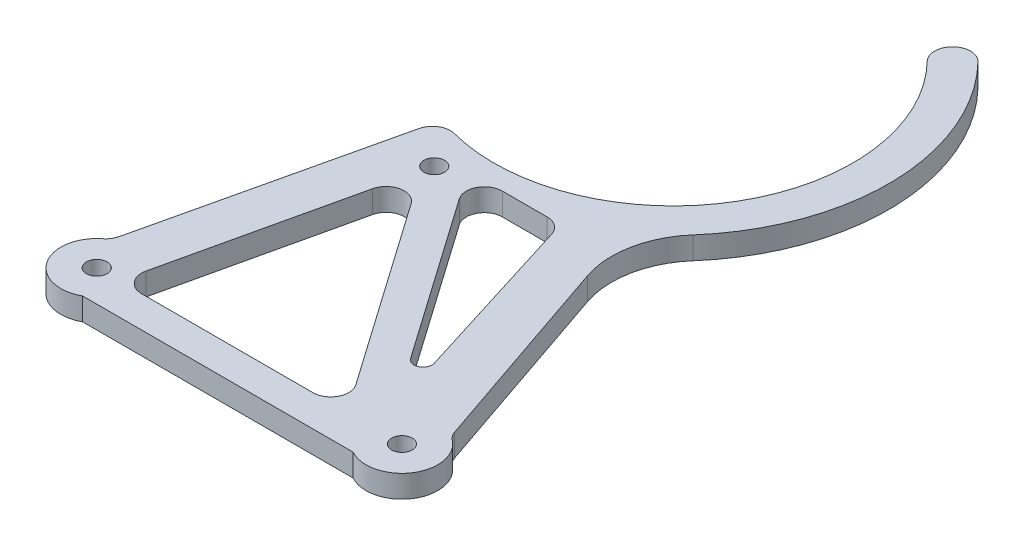
SolidWorks part; units mm, degrees
ref_plane "Front Plane" through (0, 0, 0) normal (0, 0, 1) x (1, 0, 0)
ref_plane "Top Plane" through (0, 0, 0) normal (0, 1, 0) x (1, 0, 0)
ref_plane "Right Plane" through (0, 0, 0) normal (1, 0, 0) x (0, 0, -1)
sketch "Sketch1" plane through (0, 0, 0) normal (0, 1, 0) x (1, 0, 0)
  line L0 (2.4593, 4.445) -> (40.7207, 4.445)
  line L1 (2.4593, -4.445) -> (40.7207, -4.445)
  circle A0 centre (0, 0) radius 1.4605
  circle A1 centre (0, 0) radius 5.08
  circle A2 centre (43.18, 0) radius 1.4605
  circle A3 centre (43.18, 0) radius 5.08
  dimension "D1" = 2.921
  dimension "D2" = 10.16
  dimension "D5" = 2.921
  dimension "D6" = 10.16
  dimension "D3" = 8.89
  dimension "D4" = 4.445
  dimension "D7" = 0
  dimension "D8" = 5.08
  dimension "D9" = 4.445
  dimension "D10" = 43.18
extrude "Boss-Extrude1" add sketch "Sketch1" along normal blind 3.175 contours A1 A0 | A3 L0 A1 L1 | A3 A2
sketch "Sketch3" plane through (0, 3.175, 0) normal (0, 1, 0) x (1, 0, 0)
  line L0 (31.75, 85.6456) -> (35.05, 89.5078)
  line L1 (-2.4593, 4.445) -> (35.6407, 4.445)
  line L3 (2.4593, 4.445) -> (40.7207, 4.445) construction
  line L4 (-2.4593, 4.445) -> (6.35, 42.545)
  line L5 (45.72, 4.3994) -> (33.02, 41.5706)
  arc A0 (6.35, 42.545) -> (31.75, 85.6456) centre (15.2501, 66.3347) ccw
  arc A1 (2.4593, 4.445) -> (2.4593, -4.445) centre (0, 0) ccw construction
  arc A3 (40.7207, -4.445) -> (40.7207, 4.445) centre (43.18, 0) ccw construction
  arc A4 (35.05, 89.5078) -> (33.02, 41.5706) centre (15.2501, 66.3347) cw
  circle A5 centre (43.18, 0) radius 1.4605 construction
  dimension "D1" = 25.4
  dimension "D10" = 0
  dimension "D7" = 0
  dimension "D8" = 30.48
  dimension "D2" = 160
  dimension "D3" = 25.4
  dimension "D4" = 38.1
  dimension "D5" = 0
  dimension "D6" = 6.35
  dimension "D9" = 30.48
  dimension "D11" = 5.08
  dimension "D12" = 12.7
  dimension "D13" = 2.54
extrude "Boss-Extrude3" add sketch "Sketch3" against normal blind 3.175
sketch "Sketch4" plane through (0, 3.175, 0) normal (0, 1, 0) x (1, 0, 0)
  line L2 (39.37, 0) -> (3.175, 0)
  line L3 (3.175, 0) -> (11.8398, 38.1)
  line L4 (11.8398, 38.1) -> (27.4954, 38.1)
  line L5 (27.4954, 38.1) -> (39.37, 0)
  line L6 (-2.4593, 4.445) -> (6.35, 42.545) construction
  line L7 (45.72, 4.3994) -> (33.02, 41.5706) construction
  line L8 (11.0899, 34.8025) -> (35.4588, 0)
  line L9 (14.4014, 38.1) -> (37.9988, 4.3994)
  circle A0 centre (43.18, 0) radius 1.4605 construction
  dimension "D1" = 3.175
  dimension "D2" = 3.81
  dimension "D3" = 6.35
  dimension "D4" = 6.35
  dimension "D5" = 0
  dimension "D6" = 38.1
  dimension "D7" = 55
  dimension "D8" = 55
  dimension "D9" = 5.08
  dimension "D10" = 2.54
extrude "Cut-Extrude1" cut sketch "Sketch4" against normal blind 25.4 contours L4 L9 L5 | L8 L3 L2
fillet "Fillet4" radius 2.54 5 edges at (14.4014, 1.5875, -38.1) (11.0899, 1.5875, -34.8025) (27.4954, 1.5875, -38.1) (35.4588, 1.5875, 0) (3.175, 1.5875, 0)
fillet "Fillet5" radius 12.7 1 edges at (33.02, 1.5875, -41.5706)
fillet "Fillet6" radius 2.54 5 edges at (6.35, 1.5875, -42.545) (35.05, 1.5875, -89.5078) (31.75, 1.5875, -85.6456) (-2.4593, 1.5875, -4.445) (45.72, 1.5875, -4.3994)
fillet "Fillet7" radius 1.27 1 edges at (37.9988, 1.5875, -4.3994)
sketch "Sketch5" plane through (0, 3.175, 0) normal (0, 1, 0) x (1, 0, 0)
  circle A0 centre (11.43, 36.322) radius 1.4605
  dimension "D1" = 2.921
  dimension "D2" = 11.43
  dimension "D3" = 36.322
extrude "Cut-Extrude2" cut sketch "Sketch5" against normal blind 25.4 contours A0
